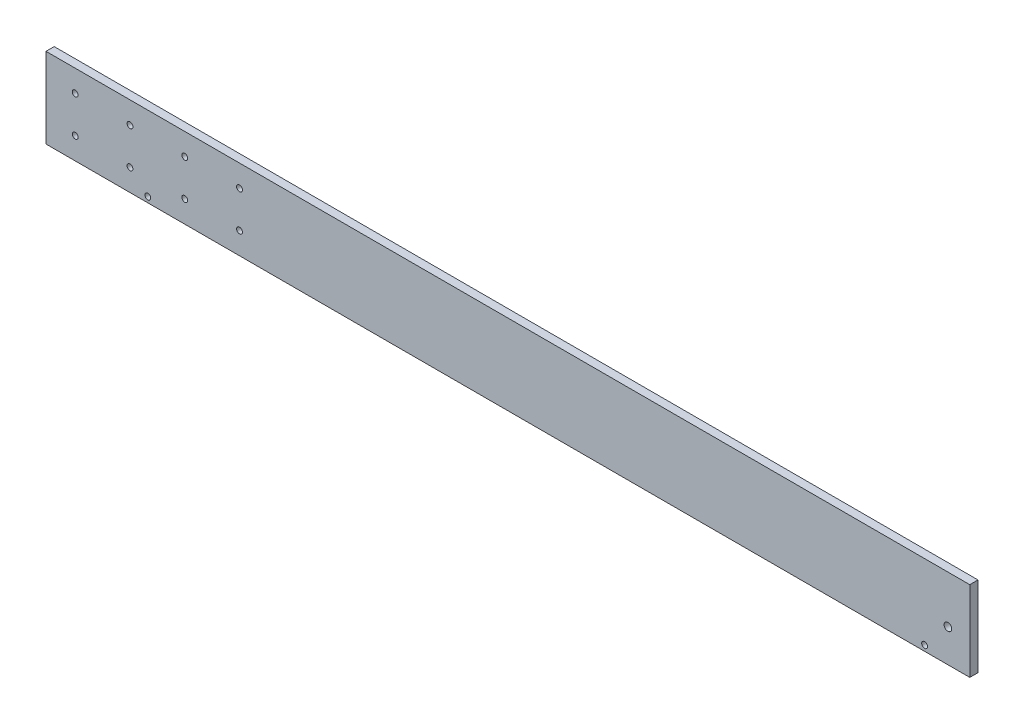
SolidWorks part; units mm, degrees
ref_plane "Front Plane" through (0, 0, 0) normal (0, 0, 1) x (1, 0, 0)
ref_plane "Top Plane" through (0, 0, 0) normal (0, 1, 0) x (1, 0, 0)
ref_plane "Right Plane" through (0, 0, 0) normal (1, 0, 0) x (0, 0, -1)
sketch "Sketch1" plane through (0, 0, 0) normal (0, 0, 1) x (1, 0, 0)
  line L0 (-253, 0) -> (-154.8681, 0) construction
  line L1 (-253, -22) -> (253, -22)
  line L2 (-253, -22) -> (-253, 22)
  line L3 (-253, 22) -> (253, 22)
  line L4 (253, -22) -> (253, 22)
  line L5 (-253, -22) -> (253, 22) construction
  line L6 (-253, 22) -> (253, -22) construction
  line L7 (-247, 6.6679) -> (-247, 39) construction
  circle A0 centre (241, -4) radius 2.1 construction
  circle A1 centre (241, -4) radius 2.1
  circle A2 centre (-237, 10) radius 1.6
  circle A3 centre (-207, 10) radius 1.6
  circle A4 centre (-177, 10) radius 1.6
  circle A5 centre (-147, 10) radius 1.6
  circle A6 centre (-207, -10) radius 1.6
  circle A7 centre (-177, -10) radius 1.6
  circle A8 centre (-147, -10) radius 1.6
  circle A9 centre (-237, -10) radius 1.6
  circle A10 centre (228.25, -19) radius 1.6 construction
  circle A11 centre (228.25, -19) radius 1.6
  circle A12 centre (-197.25, -19) radius 1.6 construction
  circle A13 centre (-197.25, -19) radius 1.6
  point P0 (0, 0)
  dimension "D3" = 3.2
  dimension "D1" = 506
  dimension "D2" = 44
  dimension "D4" = 10
  dimension "D5" = 10
  dimension "D6" = 4
  dimension "D7" = 2
extrude "Boss-Extrude1" add sketch "Sketch1" along normal blind 4.5
